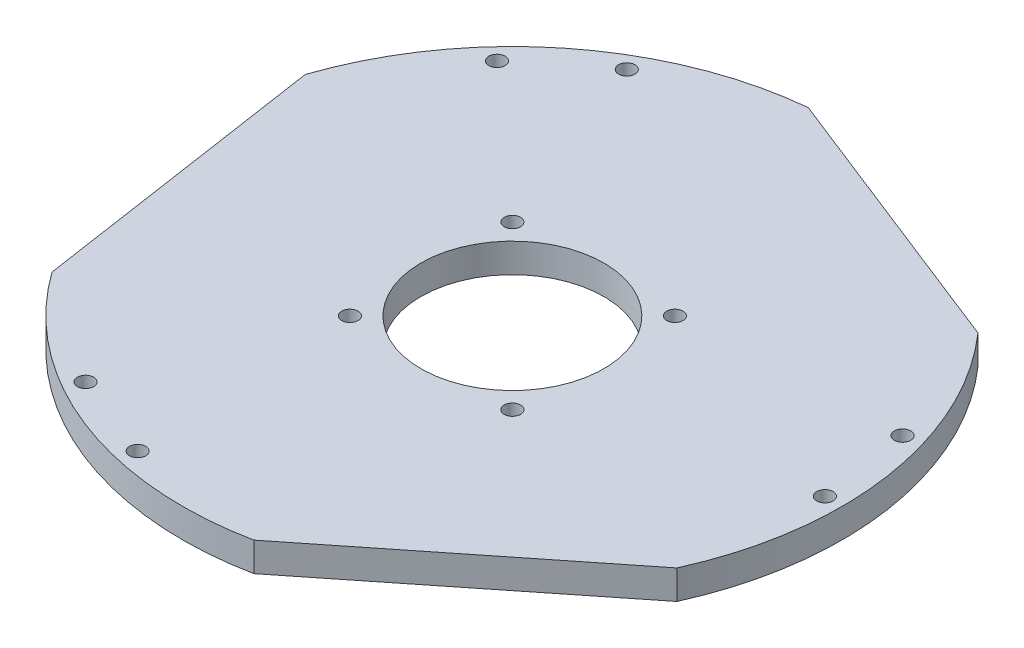
SolidWorks part; units mm, degrees
material "Oak"
ref_plane "Front Plane" through (0, 0, 0) normal (0, 0, 1) x (1, 0, 0)
ref_plane "Top Plane" through (0, 0, 0) normal (0, 1, 0) x (1, 0, 0)
ref_plane "Right Plane" through (0, 0, 0) normal (1, 0, 0) x (0, 0, -1)
sketch "Sketch1" plane through (0, 0, 0) normal (0, 0, 1) x (1, 0, 0)
  line L0 (0, -200000) -> (0, 218797.9879) construction
  line L1 (144.145, -24.4122) -> (144.145, -37.1122) construction
  line L2 (0, -24.4122) -> (144.145, -24.4122) construction
  line L3 (144.145, -37.1122) -> (0, -37.1122) construction
  line L4 (0, -200000) -> (0, 218797.9879) construction
  line L5 (144.145, -24.4122) -> (144.145, -37.1122)
  line L6 (0, -24.4122) -> (144.145, -24.4122)
  line L7 (144.145, -37.1122) -> (0, -37.1122)
  line L8 (0, -24.4122) -> (0, -37.1122)
revolve "Revolve1" add sketch "Sketch1" angle 360 about L4
hole_wizard "9/32 (0.28125) Diameter Hole1" positions "Sketch2" profile "Sketch3" hole size "9/32" standard "ANSI Inch" end condition up to next
sketch "Sketch2" plane through (0, -24.4122, 0) normal (0, 1, 0) x (1, 0, 0)
  line L0 (0, 0) -> (136.525, 0) construction
  line L3 (0, 0) -> (-68.2625, -118.2341) construction
  line L6 (0, 0) -> (-68.2625, 118.2341) construction
  line L7 (-99.8481, 93.1098) -> (0, 0) construction
  line L9 (0, 0) -> (-30.7114, -133.0259) construction
  line L12 (0, 0) -> (130.5595, 39.916) construction
  line L14 (-35.5, -35.5) -> (35.5, -35.5) construction
  line L15 (-35.5, -35.5) -> (-35.5, 35.5) construction
  line L16 (-35.5, 35.5) -> (35.5, 35.5) construction
  line L17 (35.5, -35.5) -> (35.5, 35.5) construction
  line L18 (-35.5, 0) -> (0, 0) construction
  line L19 (0, 0) -> (0, -35.5) construction
  circle A0 centre (0, 0) radius 136.525
  point P0 (136.525, 0)
  point P2 (-68.2625, -118.2341)
  point P4 (-68.2625, 118.2341)
  point P32 (-99.8481, 93.1098)
  point P57 (130.5595, 39.916)
  point P60 (-30.7114, -133.0259)
  point P138 (-35.5, -35.5)
  point P141 (-35.5, 35.5)
  point P144 (35.5, 35.5)
  point P147 (35.5, -35.5)
  dimension "D3" = 17
  dimension "D1" = 120
  dimension "D2" = 120
  dimension "D4" = 120
  dimension "D5" = 120
  dimension "D6" = 71
sketch "Sketch3" plane through (136.525, -24.4122, 0) normal (1, 0, 0) x (0, 0, 1)
  line L0 (0, 0) -> (0, 12.7)
  line L1 (0, 12.7) -> (3.5719, 12.7)
  line L2 (3.5719, 12.7) -> (3.5719, 0)
  line L5 (3.5719, 0) -> (0, 0)
  line L11 (0, -6.35) -> (0, 107.95) construction
  dimension "Thru Hole Dia." = 7.1437
  dimension "Thru Hole Depth" = 12.7
sketch "Sketch4" plane through (0, -24.4122, 0) normal (0, 1, 0) x (1, 0, 0)
  line L0 (253.7221, 37.919) -> (-94.0222, -238.6893)
  line L1 (-94.0222, -238.6893) -> (-159.6999, 200.7703)
  line L2 (-159.6999, 200.7703) -> (253.7221, 37.919)
  line L3 (253.7221, 37.919) -> (0, 0) construction
  line L4 (130.5595, 39.916) -> (136.525, 0) construction
  circle A0 centre (0, 0) radius 128.27 construction
  point P6 (133.5423, 19.958)
  dimension "D1" = 256.54
extrude "Cut-Extrude1" cut sketch "Sketch4" against normal through all flip side to cut
sketch "Sketch6" plane through (0, -24.4122, 0) normal (0, 1, 0) x (1, 0, 0)
  circle A0 centre (0, 0) radius 40
  dimension "D1" = 80
extrude "Cut-Extrude2" cut sketch "Sketch6" against normal through all
